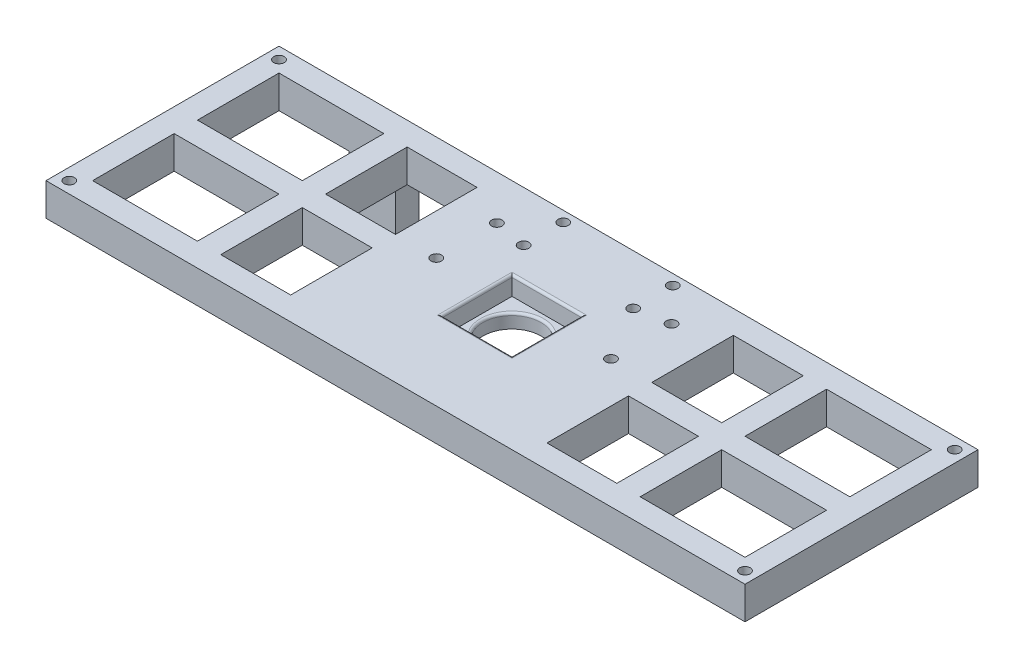
SolidWorks part; units mm, degrees
ref_plane "前视基准面" through (0, 0, 0) normal (0, 0, 1) x (1, 0, 0)
ref_plane "上视基准面" through (0, 0, 0) normal (0, 1, 0) x (1, 0, 0)
ref_plane "右视基准面" through (0, 0, 0) normal (1, 0, 0) x (0, 0, -1)
sketch "草图1" plane through (0, 0, 0) normal (0, 1, 0) x (1, 0, 0)
  line L1 (0, 0) -> (-300, 0)
  line L2 (0, 0) -> (0, 100)
  line L3 (0, 100) -> (-300, 100)
  line L4 (-300, 0) -> (-300, 100)
  dimension "D1" = 300
  dimension "D2" = 100
extrude "凸台-拉伸1" add sketch "草图1" along normal blind 16
sketch "草图2" plane through (0, 16, 0) normal (0, 1, 0) x (1, 0, 0)
  line L0 (-150, 100) -> (-150, 50) construction
  line L1 (0, 100) -> (-300, 100) construction
  line L2 (-300, 50) -> (-150, 50) construction
  line L3 (-300, 100) -> (-300, 0) construction
  line L5 (-165, 65) -> (-135, 65)
  line L6 (-165, 65) -> (-165, 35)
  line L7 (-165, 35) -> (-135, 35)
  line L8 (-135, 65) -> (-135, 35)
  line L9 (-165, 65) -> (-135, 35) construction
  line L10 (-165, 35) -> (-135, 65) construction
  dimension "D1" = 50
  dimension "D2" = 30
  dimension "D3" = 30
extrude "切除-拉伸1" cut sketch "草图2" against normal blind 8
sketch "草图3" plane through (0, 8, 0) normal (0, 1, 0) x (1, 0, 0)
  line L0 (-135, 65) -> (-165, 65) construction
  line L1 (-135, 35) -> (-135, 65) construction
  circle A0 centre (-150, 50) radius 12.5
  dimension "D3" = 25
  dimension "D1" = 15
  dimension "D2" = 15
extrude "切除-拉伸2" cut sketch "草图3" against normal blind 14
sketch "草图4" plane through (0, 16, 0) normal (0, 1, 0) x (1, 0, 0)
  line L0 (-165, 65) -> (-165, 35) construction
  line L1 (-295, 90) -> (-245, 90)
  line L2 (-295, 90) -> (-295, 55)
  line L3 (-295, 55) -> (-245, 55)
  line L4 (-245, 90) -> (-245, 55)
  line L5 (-295, 45) -> (-245, 45)
  line L6 (-295, 45) -> (-295, 10)
  line L7 (-295, 10) -> (-245, 10)
  line L8 (-245, 45) -> (-245, 10)
  line L9 (-235, 90) -> (-185, 90)
  line L10 (-235, 90) -> (-235, 55)
  line L11 (-235, 55) -> (-185, 55)
  line L12 (-185, 90) -> (-185, 55)
  line L13 (-235, 45) -> (-185, 45)
  line L14 (-235, 45) -> (-235, 10)
  line L15 (-235, 10) -> (-185, 10)
  line L16 (-185, 45) -> (-185, 10)
  line L17 (0, 100) -> (-300, 100) construction
  line L18 (-300, 0) -> (0, 0) construction
  line L19 (-300, 100) -> (-300, 0) construction
  line L20 (-150, 100) -> (-150, 73.2626) construction
  line L21 (-5, 10) -> (-55, 10)
  line L22 (-55, 45) -> (-55, 10)
  line L23 (-5, 45) -> (-55, 45)
  line L24 (-5, 45) -> (-5, 10)
  line L25 (-65, 10) -> (-115, 10)
  line L26 (-115, 45) -> (-115, 10)
  line L27 (-65, 45) -> (-115, 45)
  line L28 (-65, 45) -> (-65, 10)
  line L29 (-65, 55) -> (-115, 55)
  line L30 (-115, 90) -> (-115, 55)
  line L31 (-65, 90) -> (-115, 90)
  line L32 (-65, 90) -> (-65, 55)
  line L33 (-5, 55) -> (-55, 55)
  line L34 (-55, 90) -> (-55, 55)
  line L35 (-5, 90) -> (-55, 90)
  line L36 (-5, 90) -> (-5, 55)
  dimension "D1" = 20
  dimension "D2" = 20
  dimension "D3" = 10
  dimension "D4" = 10
  dimension "D5" = 10
  dimension "D6" = 35
  dimension "D7" = 10
  dimension "D8" = 10
  dimension "D9" = 5
  dimension "D10" = 5
  dimension "D11" = 35
  dimension "D12" = 35
  dimension "D13" = 50
  dimension "D14" = 50
  dimension "D15" = 50
  dimension "D16" = 50
extrude "切除-拉伸3" cut sketch "草图4" against normal up to next
sketch "草图7" plane through (-185, 0, 0) normal (-1, 0, 0) x (0, 0, 1)
  line L0 (-45, 0) -> (-10, 0) construction
  line L1 (-10, 0) -> (-10, 16) construction
  line L2 (-10, 16) -> (-45, 16) construction
  line L3 (-45, 16) -> (-45, 0) construction
  line L4 (-90, 0) -> (-55, 0) construction
  line L5 (-55, 0) -> (-55, 16) construction
  line L6 (-55, 16) -> (-90, 16) construction
  line L7 (-90, 16) -> (-90, 0) construction
  line L8 (-45, 0) -> (-10, 0)
  line L9 (-10, 0) -> (-10, 16)
  line L10 (-10, 16) -> (-45, 16)
  line L11 (-45, 16) -> (-45, 0)
  line L12 (-90, 0) -> (-55, 0)
  line L13 (-55, 0) -> (-55, 16)
  line L14 (-55, 16) -> (-90, 16)
  line L15 (-90, 16) -> (-90, 0)
extrude "凸台-拉伸2" add sketch "草图7" along normal blind 20
sketch "草图8" plane through (-115, 0, 0) normal (1, 0, 0) x (0, 0, -1)
  line L0 (10, 0) -> (45, 0) construction
  line L1 (45, 0) -> (45, 16) construction
  line L2 (45, 16) -> (10, 16) construction
  line L3 (10, 16) -> (10, 0) construction
  line L4 (55, 0) -> (90, 0) construction
  line L5 (90, 0) -> (90, 16) construction
  line L6 (90, 16) -> (55, 16) construction
  line L7 (55, 16) -> (55, 0) construction
  line L8 (10, 0) -> (45, 0)
  line L9 (45, 0) -> (45, 16)
  line L10 (45, 16) -> (10, 16)
  line L11 (10, 16) -> (10, 0)
  line L12 (55, 0) -> (90, 0)
  line L13 (90, 0) -> (90, 16)
  line L14 (90, 16) -> (55, 16)
  line L15 (55, 16) -> (55, 0)
extrude "凸台-拉伸3" add sketch "草图8" along normal blind 20
sketch "草图9" plane through (0, 0, 0) normal (0, -1, 0) x (1, 0, 0)
  line L5 (-295, -90) -> (-245, -90) construction
  line L10 (-260, -90) -> (-240, -90)
  line L20 (-260, -90) -> (-260, -100)
  line L21 (-260, -100) -> (-240, -100)
  line L22 (-240, -90) -> (-240, -100)
  line L23 (0, -100) -> (-300, -100) construction
  line L24 (-300, -100) -> (-300, 0) construction
  dimension "D3" = 20
  dimension "D4" = 40
extrude "凸台-拉伸4" add sketch "草图9" along normal blind 25
fillet "圆角1" radius 1 1 edges at (-150, 8, -37.5)
fillet "圆角2" radius 1 4 edges at (-135, 16, -50) (-150, 16, -65) (-150, 16, -35) (-165, 16, -50)
sketch "草图13" plane through (-5, 0, 0) normal (-1, 0, 0) x (0, 0, 1)
  line L0 (-90, 0) -> (-55, 0) construction
  line L1 (-55, 0) -> (-55, 16) construction
  line L2 (-55, 16) -> (-90, 16) construction
  line L3 (-90, 16) -> (-90, 0) construction
  line L4 (-45, 0) -> (-10, 0) construction
  line L5 (-10, 0) -> (-10, 16) construction
  line L6 (-10, 16) -> (-45, 16) construction
  line L7 (-45, 16) -> (-45, 0) construction
  line L8 (-90, 0) -> (-55, 0)
  line L9 (-55, 0) -> (-55, 16)
  line L10 (-55, 16) -> (-90, 16)
  line L11 (-90, 16) -> (-90, 0)
  line L12 (-45, 0) -> (-10, 0)
  line L13 (-10, 0) -> (-10, 16)
  line L14 (-10, 16) -> (-45, 16)
  line L15 (-45, 16) -> (-45, 0)
extrude "凸台-拉伸6" add sketch "草图13" along normal blind 4
sketch "草图14" plane through (-295, 0, 0) normal (1, 0, 0) x (0, 0, -1)
  line L0 (55, 0) -> (90, 0) construction
  line L1 (90, 0) -> (90, 16) construction
  line L2 (90, 16) -> (55, 16) construction
  line L3 (55, 16) -> (55, 0) construction
  line L4 (10, 0) -> (45, 0) construction
  line L5 (45, 0) -> (45, 16) construction
  line L6 (45, 16) -> (10, 16) construction
  line L7 (10, 16) -> (10, 0) construction
  line L8 (55, 0) -> (90, 0)
  line L9 (90, 0) -> (90, 16)
  line L10 (90, 16) -> (55, 16)
  line L11 (55, 16) -> (55, 0)
  line L12 (10, 0) -> (45, 0)
  line L13 (45, 0) -> (45, 16)
  line L14 (45, 16) -> (10, 16)
  line L15 (10, 16) -> (10, 0)
extrude "凸台-拉伸7" add sketch "草图14" along normal blind 4
sketch "草图17" plane through (-291, 0, 0) normal (1, 0, 0) x (0, 0, -1)
  line L0 (10, 16) -> (10, 0) construction
  line L1 (10, 0) -> (45, 0) construction
  line L2 (45, 0) -> (45, 16) construction
  line L3 (45, 16) -> (10, 16) construction
  line L4 (55, 16) -> (55, 0) construction
  line L5 (55, 0) -> (90, 0) construction
  line L6 (90, 0) -> (90, 16) construction
  line L7 (90, 16) -> (55, 16) construction
  line L8 (10, 16) -> (10, 0)
  line L9 (10, 0) -> (45, 0)
  line L10 (45, 0) -> (45, 16)
  line L11 (45, 16) -> (10, 16)
  line L12 (55, 16) -> (55, 0)
  line L13 (55, 0) -> (90, 0)
  line L14 (90, 0) -> (90, 16)
  line L15 (90, 16) -> (55, 16)
extrude "凸台-拉伸8" add sketch "草图17" along normal blind 1
sketch "草图18" plane through (-9, 0, 0) normal (-1, 0, 0) x (0, 0, 1)
  line L0 (-45, 16) -> (-45, 0) construction
  line L1 (-45, 0) -> (-10, 0) construction
  line L2 (-10, 0) -> (-10, 16) construction
  line L3 (-10, 16) -> (-45, 16) construction
  line L4 (-90, 16) -> (-90, 0) construction
  line L5 (-90, 0) -> (-55, 0) construction
  line L6 (-55, 0) -> (-55, 16) construction
  line L7 (-55, 16) -> (-90, 16) construction
  line L8 (-45, 16) -> (-45, 0)
  line L9 (-45, 0) -> (-10, 0)
  line L10 (-10, 0) -> (-10, 16)
  line L11 (-10, 16) -> (-45, 16)
  line L12 (-90, 16) -> (-90, 0)
  line L13 (-90, 0) -> (-55, 0)
  line L14 (-55, 0) -> (-55, 16)
  line L15 (-55, 16) -> (-90, 16)
extrude "凸台-拉伸9" add sketch "草图18" along normal blind 1
sketch "草图19" plane through (0, 16, 0) normal (0, 1, 0) x (1, 0, 0)
  line L0 (-300, 100) -> (-295, 100) construction
  line L1 (0, 100) -> (-300, 100) construction
  line L2 (-295, 100) -> (-295, 95) construction
  line L3 (-150, 100) -> (-150, 83.4567) construction
  line L4 (-300, 50) -> (-202.8605, 50) construction
  line L5 (-300, 100) -> (-300, 0) construction
  line L6 (-150, 0) -> (-150, 22.48) construction
  line L7 (-300, 0) -> (0, 0) construction
  line L8 (-5, 100) -> (-5, 95) construction
  line L9 (0, 100) -> (-5, 100) construction
  circle A0 centre (-295, 95) radius 2.25
  circle A1 centre (-295, 5) radius 2.25
  circle A4 centre (-5, 5) radius 2.25
  circle A5 centre (-5, 95) radius 2.25
  dimension "D3" = 4.5
  dimension "D1" = 5
  dimension "D2" = 5
extrude "切除-拉伸8" cut sketch "草图19" against normal blind 5
sketch "草图20" plane through (0, 0, 0) normal (0, -1, 0) x (1, 0, 0)
  circle A2 centre (-295, -95) radius 2.25 construction
  circle A3 centre (-295, -5) radius 2.25 construction
  circle A6 centre (-295, -95) radius 2.25
  circle A7 centre (-295, -5) radius 2.25
  circle A8 centre (-5, -95) radius 2.25 construction
  circle A9 centre (-5, -5) radius 2.25 construction
  circle A10 centre (-5, -95) radius 2.25
  circle A11 centre (-5, -5) radius 2.25
extrude "切除-拉伸9" cut sketch "草图20" against normal blind 7
extrude "切除-拉伸10" cut sketch "草图21" against normal blind 5
sketch "草图21" plane through (-100.2762, 16, -200.0918) normal (0, 1, 0) x (-0.0018, 0, -1)
  circle A4 centre (-104.5433, 26.4163) radius 1.45
  circle A5 centre (-121.5433, 26.4476) radius 1.45
  circle A6 centre (-121.4568, 73.4475) radius 1.45
  circle A7 centre (-104.4568, 73.4162) radius 1.45
sketch "草图22" plane through (0, 16, 0) normal (0, 1, 0) x (1, 0, 0)
  circle A0 centre (-173.5, 95.5) radius 2.25
  circle A1 centre (-173.5, 78.5) radius 2.25
  circle A2 centre (-126.5, 95.5) radius 2.25
  circle A3 centre (-126.5, 78.5) radius 2.25
  dimension "D1" = 4.5
  dimension "D2" = 4.5
  dimension "D3" = 4.5
  dimension "D4" = 4.5
extrude "切除-拉伸11" cut sketch "草图22" against normal blind 5
extrude "切除-拉伸12" cut sketch "草图23" against normal blind 5
sketch "草图23" plane through (-100.2762, 16, -200.0918) normal (0, 1, 0) x (-0.0018, 0, -1)
  circle A4 centre (-119.0691, 12.4622) radius 1.45
  circle A5 centre (-145.069, 12.51) radius 1.45
  circle A6 centre (-144.931, 87.4716) radius 1.45
  circle A7 centre (-118.9311, 87.4237) radius 1.45
sketch "草图24" plane through (0, 16, 0) normal (0, 1, 0) x (1, 0, 0)
  circle A0 centre (-187.4808, 81) radius 2.25
  circle A1 centre (-187.4808, 55) radius 2.25
  circle A2 centre (-112.5192, 81) radius 2.25
  circle A3 centre (-112.5192, 55) radius 2.25
  dimension "D1" = 4.5
  dimension "D2" = 4.5
  dimension "D3" = 4.5
  dimension "D4" = 4.5
extrude "切除-拉伸13" cut sketch "草图24" against normal blind 5
sketch "草图26" plane through (0, 0, 0) normal (0, -1, 0) x (1, 0, 0)
  line L12 (-260, -90) -> (-290, -90)
  line L13 (-290, -90) -> (-290, -55)
  line L14 (-290, -55) -> (-245, -55)
  line L15 (-245, -55) -> (-245, -90)
  line L16 (-245, -90) -> (-240, -90)
  line L17 (-240, -90) -> (-240, -100)
  line L18 (-240, -100) -> (0, -100)
  line L19 (0, -100) -> (0, 0)
  line L20 (0, 0) -> (-300, 0)
  line L21 (-300, 0) -> (-300, -100)
  line L22 (-300, -100) -> (-260, -100)
  line L23 (-260, -100) -> (-260, -90)
  line L24 (-260, -90) -> (-290, -90)
  line L25 (-290, -90) -> (-290, -55)
  line L26 (-290, -55) -> (-245, -55)
  line L27 (-245, -55) -> (-245, -90)
  line L28 (-245, -90) -> (-240, -90)
  line L29 (-240, -90) -> (-240, -100)
  line L30 (-240, -100) -> (0, -100)
  line L31 (0, -100) -> (0, 0)
  line L32 (0, 0) -> (-300, 0)
  line L33 (-300, 0) -> (-300, -100)
  line L34 (-300, -100) -> (-260, -100)
  line L35 (-260, -100) -> (-260, -90)
  dimension "D1" = 0
extrude "切除-拉伸15" cut sketch "草图26" against normal blind 2
sketch "草图27" plane through (0, 11, 0) normal (0, 1, 0) x (1, 0, 0)
  circle A0 centre (-173.5, 95.5) radius 1.5
  circle A1 centre (-187.4808, 81) radius 1.5
  circle A2 centre (-173.5, 78.5) radius 1.5
  circle A3 centre (-126.5, 95.5) radius 1.5
  circle A4 centre (-126.5, 78.5) radius 1.5
  circle A5 centre (-187.4808, 55) radius 1.5
  circle A6 centre (-112.5192, 55) radius 1.5
  circle A7 centre (-112.5192, 81) radius 1.5
  circle A8 centre (-5, 95) radius 1.5
  circle A9 centre (-5, 5) radius 1.5
  circle A10 centre (-295, 5) radius 1.5
  circle A11 centre (-295, 95) radius 1.5
  dimension "D1" = 3
extrude "切除-拉伸16" cut sketch "草图27" against normal blind 4
